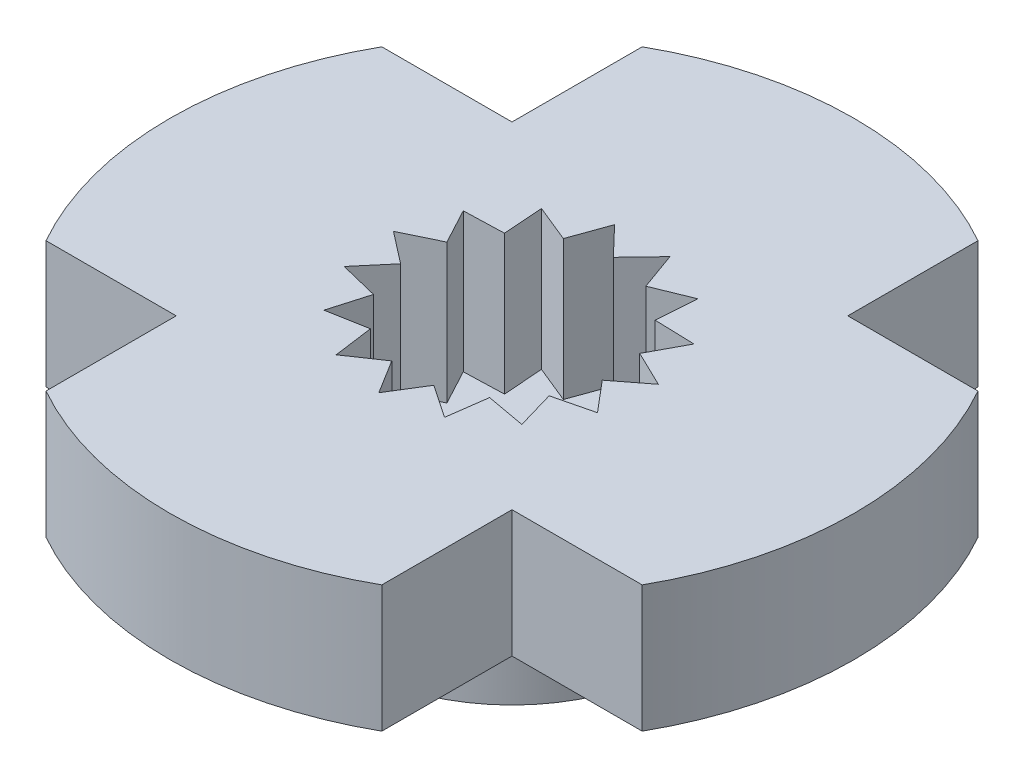
SolidWorks part; units mm, degrees
ref_plane "正面" through (0, 0, 0) normal (0, 0, 1) x (1, 0, 0)
ref_plane "平面" through (0, 0, 0) normal (0, 1, 0) x (1, 0, 0)
ref_plane "右側面" through (0, 0, 0) normal (1, 0, 0) x (0, 0, -1)
sketch "ｽｹｯﾁ1" plane through (0, 0, 0) normal (0, 1, 0) x (1, 0, 0)
  line L30 (0, 1.6) -> (0.437, 2.056) construction
  line L31 (0.6508, 1.4617) -> (1.2355, 1.7005) construction
  line L32 (0.6508, 1.4617) -> (0.437, 2.056) construction
  line L33 (1.189, 1.0706) -> (1.8203, 1.051) construction
  line L34 (1.189, 1.0706) -> (1.2355, 1.7005) construction
  line L35 (1.5217, 0.4944) -> (2.0904, 0.2197) construction
  line L36 (1.5217, 0.4944) -> (1.8203, 1.051) construction
  line L37 (1.5912, -0.1672) -> (1.9991, -0.6495) construction
  line L38 (1.5912, -0.1672) -> (2.0904, 0.2197) construction
  line L39 (1.3856, -0.8) -> (1.562, -1.4065) construction
  line L40 (1.3856, -0.8) -> (1.9991, -0.6495) construction
  line L41 (0.9405, -1.2944) -> (0.8549, -1.9202) construction
  line L42 (0.9405, -1.2944) -> (1.562, -1.4065) construction
  line L43 (0.3327, -1.565) -> (0, -2.1019) construction
  line L44 (0.3327, -1.565) -> (0.8549, -1.9202) construction
  line L45 (-0.3327, -1.565) -> (-0.8549, -1.9202) construction
  line L46 (-0.3327, -1.565) -> (0, -2.1019) construction
  line L47 (-0.9405, -1.2944) -> (-1.562, -1.4065) construction
  line L48 (-0.9405, -1.2944) -> (-0.8549, -1.9202) construction
  line L49 (-1.3856, -0.8) -> (-1.9991, -0.6495) construction
  line L50 (-1.3856, -0.8) -> (-1.562, -1.4065) construction
  line L51 (-1.5912, -0.1672) -> (-2.0904, 0.2197) construction
  line L52 (-1.5912, -0.1672) -> (-1.9991, -0.6495) construction
  line L53 (-1.5217, 0.4944) -> (-1.8203, 1.051) construction
  line L54 (-1.5217, 0.4944) -> (-2.0904, 0.2197) construction
  line L55 (-1.189, 1.0706) -> (-1.2355, 1.7005) construction
  line L56 (-1.189, 1.0706) -> (-1.8203, 1.051) construction
  line L57 (-0.6508, 1.4617) -> (-0.437, 2.056) construction
  line L58 (-0.6508, 1.4617) -> (-1.2355, 1.7005) construction
  line L59 (0, 1.6) -> (-0.437, 2.056) construction
  line L60 (2.65, 4.7051) -> (2.65, 2.65)
  line L61 (-2.65, 4.7051) -> (-2.65, 2.65)
  line L63 (-4.7051, 2.65) -> (-2.65, 2.65)
  line L64 (-4.7051, -2.65) -> (-2.65, -2.65)
  line L65 (-2.65, -2.65) -> (-2.65, -4.7051)
  line L66 (2.65, -2.65) -> (2.65, -4.7051)
  line L67 (2.65, 2.65) -> (4.7051, 2.65)
  line L68 (2.65, -2.65) -> (4.7051, -2.65)
  arc A2 (-4.7051, 2.65) -> (-4.7051, -2.65) centre (0, 0) ccw
  arc A3 (2.65, 4.7051) -> (-2.65, 4.7051) centre (0, 0) ccw
  arc A4 (4.7051, -2.65) -> (4.7051, 2.65) centre (0, 0) ccw
  arc A5 (-2.65, -4.7051) -> (2.65, -4.7051) centre (0, 0) ccw
extrude "ﾎﾞｽ - 押し出し1" add sketch "ｽｹｯﾁ1" along normal blind 2
sketch "ｽｹｯﾁ2" plane through (0, 0, 0) normal (0, -1, 0) x (1, 0, 0)
  circle A0 centre (0, 0) radius 2.575
  circle A1 centre (0, 0) radius 0.85
  dimension "D1" = 5.15
  dimension "D2" = 1.7
extrude "ﾎﾞｽ - 押し出し2" add sketch "ｽｹｯﾁ2" along normal blind 1.5
sketch "ｽｹｯﾁ3" plane through (0, -1.5, 0) normal (0, -1, 0) x (1, 0, 0)
  circle A0 centre (0, 0) radius 1.55
  dimension "D1" = 3.1
extrude "ｶｯﾄ - 押し出し1" [suppressed] cut sketch "ｽｹｯﾁ3" against normal blind 0.3
sketch "ｽｹｯﾁ4" plane through (0, 2, 0) normal (0, 1, 0) x (1, 0, 0)
  line L0 (0, 0) -> (0, 2.4324) construction
  line L1 (0, 0) -> (0.5057, 2.3792) construction
  line L2 (0, 0) -> (0.9893, 2.2221) construction
  line L3 (0, 0) -> (1.4297, 1.9678) construction
  line L4 (0, 0) -> (1.8076, 1.6276) construction
  line L5 (0, 0) -> (2.1065, 1.2162) construction
  line L6 (0, 0) -> (2.3133, 0.7516) construction
  line L7 (0, 0) -> (2.419, 0.2543) construction
  line L24 (0, 0) -> (2.419, -0.2543) construction
  line L25 (0, 0) -> (2.3133, -0.7516) construction
  line L26 (0, 0) -> (2.1065, -1.2162) construction
  line L27 (0, 0) -> (1.8076, -1.6276) construction
  line L28 (0, 0) -> (1.4297, -1.9678) construction
  line L29 (0, 0) -> (0.9893, -2.2221) construction
  line L30 (0, 0) -> (0.5057, -2.3792) construction
  line L31 (0, 0) -> (0, -2.4324) construction
  line L32 (0, 0) -> (-0.5057, -2.3792) construction
  line L33 (0, 0) -> (-0.9893, -2.2221) construction
  line L34 (0, 0) -> (-1.4297, -1.9678) construction
  line L35 (0, 0) -> (-1.8076, -1.6276) construction
  line L36 (0, 0) -> (-2.1065, -1.2162) construction
  line L37 (0, 0) -> (-2.3133, -0.7516) construction
  line L38 (0, 0) -> (-2.419, -0.2543) construction
  line L39 (0, 0) -> (-2.419, 0.2543) construction
  line L40 (0, 0) -> (-2.3133, 0.7516) construction
  line L41 (0, 0) -> (-2.1065, 1.2162) construction
  line L42 (0, 0) -> (-1.8076, 1.6276) construction
  line L43 (0, 0) -> (-1.4297, 1.9678) construction
  line L44 (0, 0) -> (-0.9893, 2.2221) construction
  line L45 (0, 0) -> (-0.5057, 2.3792) construction
  line L46 (0, 1.6) -> (0.437, 2.056)
  line L47 (0.6508, 1.4617) -> (1.2355, 1.7005)
  line L48 (0.6508, 1.4617) -> (0.437, 2.056)
  line L49 (1.189, 1.0706) -> (1.8203, 1.051)
  line L50 (1.189, 1.0706) -> (1.2355, 1.7005)
  line L51 (1.5217, 0.4944) -> (2.0904, 0.2197)
  line L52 (1.5217, 0.4944) -> (1.8203, 1.051)
  line L53 (1.5912, -0.1672) -> (1.9991, -0.6495)
  line L54 (1.5912, -0.1672) -> (2.0904, 0.2197)
  line L55 (1.3856, -0.8) -> (1.562, -1.4065)
  line L56 (1.3856, -0.8) -> (1.9991, -0.6495)
  line L57 (0.9405, -1.2944) -> (0.8549, -1.9202)
  line L58 (0.9405, -1.2944) -> (1.562, -1.4065)
  line L59 (0.3327, -1.565) -> (0, -2.1019)
  line L60 (0.3327, -1.565) -> (0.8549, -1.9202)
  line L61 (-0.3327, -1.565) -> (-0.8549, -1.9202)
  line L62 (-0.3327, -1.565) -> (0, -2.1019)
  line L63 (-0.9405, -1.2944) -> (-1.562, -1.4065)
  line L64 (-0.9405, -1.2944) -> (-0.8549, -1.9202)
  line L65 (-1.3856, -0.8) -> (-1.9991, -0.6495)
  line L66 (-1.3856, -0.8) -> (-1.562, -1.4065)
  line L67 (-1.5912, -0.1672) -> (-2.0904, 0.2197)
  line L68 (-1.5912, -0.1672) -> (-1.9991, -0.6495)
  line L69 (-1.5217, 0.4944) -> (-1.8203, 1.051)
  line L70 (-1.5217, 0.4944) -> (-2.0904, 0.2197)
  line L71 (-1.189, 1.0706) -> (-1.2355, 1.7005)
  line L72 (-1.189, 1.0706) -> (-1.8203, 1.051)
  line L73 (-0.6508, 1.4617) -> (-0.437, 2.056)
  line L74 (-0.6508, 1.4617) -> (-1.2355, 1.7005)
  line L75 (0, 1.6) -> (-0.437, 2.056)
  circle A0 centre (0, 0) radius 1.95 construction
  circle A1 centre (0, 0) radius 1.6 construction
  point P50 (0, 0)
  point P73 (0, 0)
  point P81 (0, 0)
  dimension "D2" = 3.9
  dimension "D3" = 3.2
extrude "ｶｯﾄ - 押し出し2" cut sketch "ｽｹｯﾁ4" against normal blind 2.2
